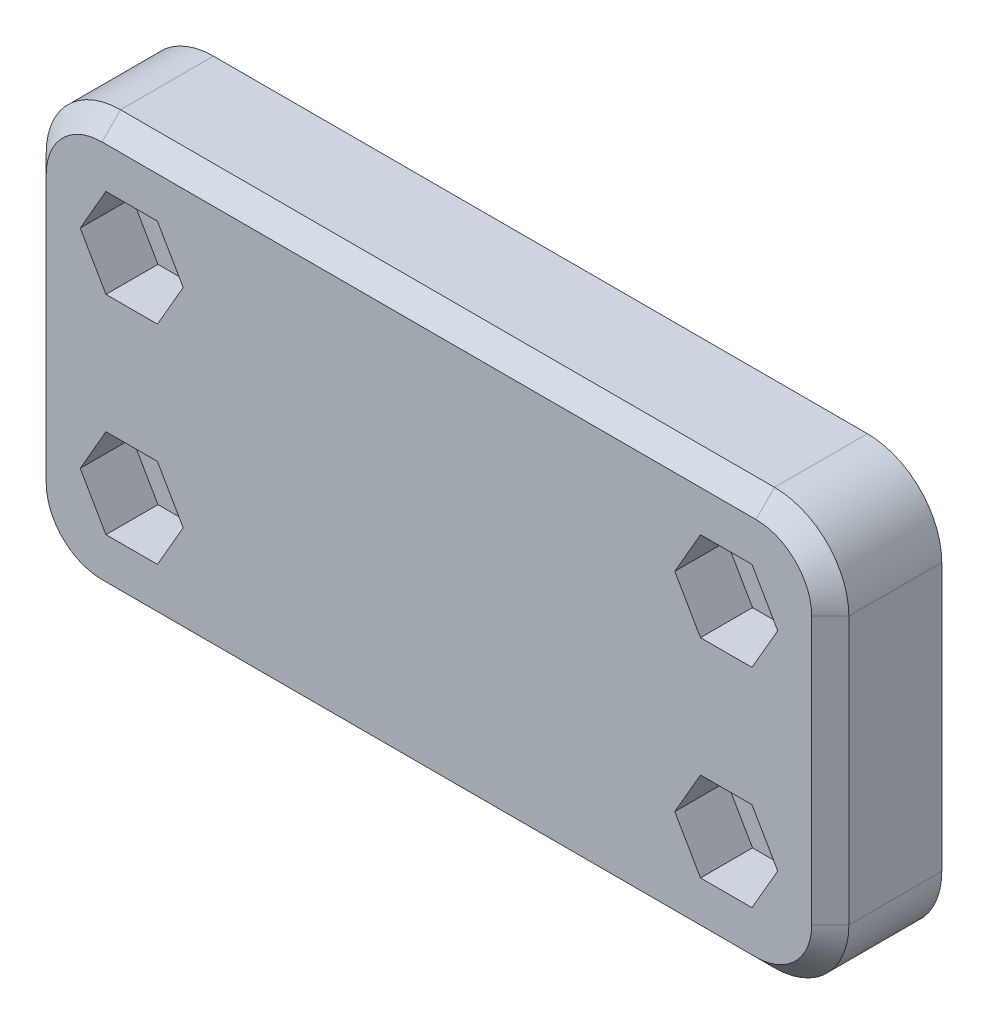
SolidWorks part; units mm, degrees
note: The reader was unsure of these and kept them because the rebuilt part matched: shared geometry of "Base<3>".
ref_plane "Front Plane" through (0, 0, 0) normal (0, 0, 1) x (1, 0, 0)
ref_plane "Top Plane" through (0, 0, 0) normal (0, 1, 0) x (1, 0, 0)
ref_plane "Right Plane" through (0, 0, 0) normal (1, 0, 0) x (0, 0, -1)
sketch "Base" plane through (0, 0, 0) normal (0, 0, 1) x (1, 0, 0)
  line L0 (-27, 14) -> (27, 14)
  line L1 (-20, 7) -> (20, 7) construction
  line L2 (-20, 7) -> (-20, -7) construction
  line L3 (-20, -7) -> (20, -7) construction
  line L4 (20, 7) -> (20, -7) construction
  line L5 (-20, 7) -> (20, -7) construction
  line L6 (-20, -7) -> (20, 7) construction
  line L7 (27, 14) -> (27, -14)
  line L8 (-27, -14) -> (27, -14)
  line L9 (-27, 14) -> (-27, -14)
  line L11 (-16.5359, 7) -> (-18.2679, 10)
  line L12 (-18.2679, 10) -> (-21.7321, 10)
  line L13 (-21.7321, 10) -> (-23.4641, 7)
  line L14 (-23.4641, 7) -> (-21.7321, 4)
  line L15 (-21.7321, 4) -> (-18.2679, 4)
  line L16 (-18.2679, 4) -> (-16.5359, 7)
  line L17 (23.4641, 7) -> (21.7321, 10)
  line L18 (21.7321, 10) -> (18.2679, 10)
  line L19 (18.2679, 10) -> (16.5359, 7)
  line L20 (16.5359, 7) -> (18.2679, 4)
  line L21 (18.2679, 4) -> (21.7321, 4)
  line L22 (21.7321, 4) -> (23.4641, 7)
  line L23 (23.4641, -7) -> (21.7321, -4)
  line L24 (21.7321, -4) -> (18.2679, -4)
  line L25 (18.2679, -4) -> (16.5359, -7)
  line L26 (16.5359, -7) -> (18.2679, -10)
  line L27 (18.2679, -10) -> (21.7321, -10)
  line L28 (21.7321, -10) -> (23.4641, -7)
  line L29 (-18.2679, -10) -> (-16.5359, -7)
  line L30 (-16.5359, -7) -> (-18.2679, -4)
  line L31 (-18.2679, -4) -> (-21.7321, -4)
  line L32 (-21.7321, -4) -> (-23.4641, -7)
  line L33 (-23.4641, -7) -> (-21.7321, -10)
  line L34 (-21.7321, -10) -> (-18.2679, -10)
  circle A0 centre (-20, 7) radius 3 construction
  circle A1 centre (20, 7) radius 3 construction
  circle A2 centre (20, -7) radius 3 construction
  circle A3 centre (-20, -7) radius 3 construction
  circle A4 centre (-20, 7) radius 1.55
  circle A5 centre (20, 7) radius 1.55
  circle A6 centre (20, -7) radius 1.55
  circle A7 centre (-20, -7) radius 1.55
  point P0 (0, 0)
  dimension "D4" = 6
  dimension "D5" = 3.1
  dimension "D1" = 14
  dimension "D2" = 40
  dimension "D3" = 7
extrude "Boss-Extrude1" add sketch "Base" along normal blind 4 contours L0 L9 L8 L7 L34 L33 L32 L31 L30 L29 L28 L27 L26 L25 L24 L23 L22 L21 L20 L19 L18 L17 L16 L15 L14 L13 L12 L11 | L27 L28 L23 L24 L25 L26 A6 | L21 L22 L17 L18 L19 L20 A5 | L33 L34 L29 L30 L31 L32 A7 | L15 L16 L11 L12 L13 L14 A4 | A4 | A5
extrude "Boss-Extrude2" add sketch "Base<3>" along normal blind 3.5 from surface at 4 contours L0 L9 L8 L7 L34 L33 L32 L31 L30 L29 L28 L27 L26 L25 L24 L23 L22 L21 L20 L19 L18 L17 L16 L15 L14 L13 L12 L11 starting at face at (-18.45, 7, 4)
sketch "Base<3>" plane through (0, 0, 0) normal (0, 0, 1) x (1, 0, 0) same geometry as "Base"
fillet "Fillet1" radius 5 4 edges at (-27, 14, 3.75) (27, 14, 3.75) (27, -14, 3.75) (-27, -14, 3.75)
chamfer "Chamfer1" distance 1.25 angle 45 8 edges at (27, 0, 7.5) (25.5355, -12.5355, 7.5) (25.5355, 12.5355, 7.5) (0, -14, 7.5) (0, 14, 7.5) (-25.5355, -12.5355, 7.5) (-25.5355, 12.5355, 7.5) (-27, 0, 7.5)
